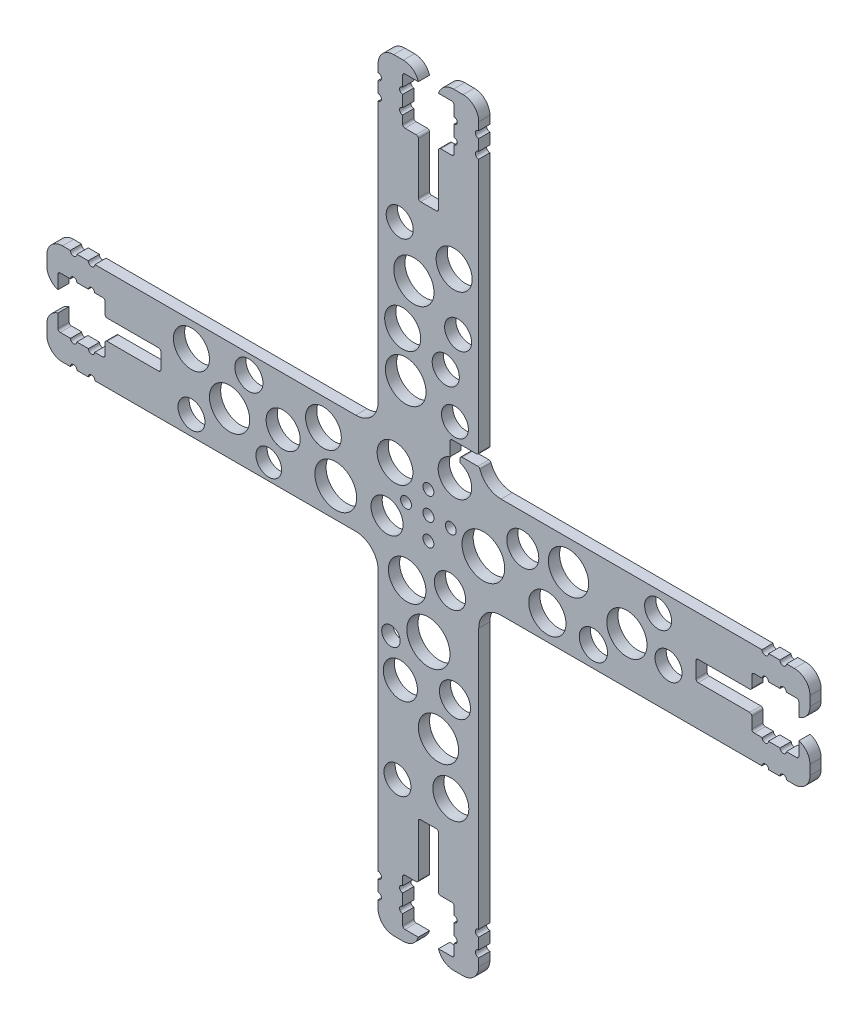
SolidWorks part; units mm, degrees
ref_plane "Front Plane" through (0, 0, 0) normal (0, 0, 1) x (1, 0, 0)
ref_plane "Top Plane" through (0, 0, 0) normal (0, 1, 0) x (1, 0, 0)
ref_plane "Right Plane" through (0, 0, 0) normal (1, 0, 0) x (0, 0, -1)
sketch "Esquisse1" plane through (0, 0, 0) normal (0, 0, 1) x (1, 0, 0)
  line L0 (0, 159.2308) -> (0, -15.7846) construction
  line L1 (-22.5, 22.5) -> (-22.5, 170.6346)
  line L2 (-22.5, 170.6346) -> (-4.5, 170.6346)
  line L3 (-4.5, 170.6346) -> (-4.5, 165.6346)
  line L4 (-4.5, 165.6346) -> (-11.5, 165.6346)
  line L5 (-11.5, 165.6346) -> (-11.5, 144.6346)
  line L6 (-11.5, 144.6346) -> (-4.5, 144.6346)
  line L7 (-4.5, 144.6346) -> (-4.5, 119.6346)
  line L8 (-4.5, 119.6346) -> (4.5, 119.6346)
  line L9 (4.5, 119.6346) -> (4.5, 144.6346)
  line L10 (4.5, 144.6346) -> (11.5, 144.6346)
  line L11 (11.5, 144.6346) -> (11.5, 165.6346)
  line L12 (11.5, 165.6346) -> (4.5, 165.6346)
  line L13 (4.5, 165.6346) -> (4.5, 170.6346)
  line L14 (4.5, 170.6346) -> (22.5, 170.6346)
  line L15 (22.5, 170.6346) -> (22.5, 22.5)
  line L16 (22.5, 22.5) -> (170.6346, 22.5)
  line L17 (170.6346, 22.5) -> (170.6346, 4.5)
  line L18 (170.6346, 4.5) -> (165.6346, 4.5)
  line L19 (165.6346, 4.5) -> (165.6346, 11.5)
  line L20 (165.6346, 11.5) -> (144.6346, 11.5)
  line L21 (144.6346, 11.5) -> (144.6346, 4.5)
  line L22 (144.6346, 4.5) -> (119.6346, 4.5)
  line L23 (119.6346, 4.5) -> (119.6346, -4.5)
  line L24 (119.6346, -4.5) -> (144.6346, -4.5)
  line L25 (144.6346, -4.5) -> (144.6346, -11.5)
  line L26 (144.6346, -11.5) -> (165.6346, -11.5)
  line L27 (165.6346, -11.5) -> (165.6346, -4.5)
  line L28 (165.6346, -4.5) -> (170.6346, -4.5)
  line L29 (170.6346, -4.5) -> (170.6346, -22.5)
  line L30 (170.6346, -22.5) -> (22.5, -22.5)
  line L31 (22.5, -22.5) -> (22.5, -170.6346)
  line L32 (22.5, -170.6346) -> (4.5, -170.6346)
  line L33 (4.5, -170.6346) -> (4.5, -165.6346)
  line L34 (4.5, -165.6346) -> (11.5, -165.6346)
  line L35 (11.5, -165.6346) -> (11.5, -144.6346)
  line L36 (11.5, -144.6346) -> (4.5, -144.6346)
  line L37 (4.5, -144.6346) -> (4.5, -119.6346)
  line L38 (4.5, -119.6346) -> (-4.5, -119.6346)
  line L39 (-4.5, -119.6346) -> (-4.5, -144.6346)
  line L40 (-4.5, -144.6346) -> (-11.5, -144.6346)
  line L41 (-11.5, -144.6346) -> (-11.5, -165.6346)
  line L42 (-11.5, -165.6346) -> (-4.5, -165.6346)
  line L43 (-4.5, -165.6346) -> (-4.5, -170.6346)
  line L44 (-4.5, -170.6346) -> (-22.5, -170.6346)
  line L45 (-22.5, -170.6346) -> (-22.5, -22.5)
  line L46 (-22.5, -22.5) -> (-170.6346, -22.5)
  line L47 (-170.6346, -22.5) -> (-170.6346, -4.5)
  line L48 (-170.6346, -4.5) -> (-165.6346, -4.5)
  line L49 (-165.6346, -4.5) -> (-165.6346, -11.5)
  line L50 (-165.6346, -11.5) -> (-144.6346, -11.5)
  line L51 (-144.6346, -11.5) -> (-144.6346, -4.5)
  line L52 (-144.6346, -4.5) -> (-119.6346, -4.5)
  line L53 (-119.6346, -4.5) -> (-119.6346, 4.5)
  line L54 (-119.6346, 4.5) -> (-144.6346, 4.5)
  line L55 (-144.6346, 4.5) -> (-144.6346, 11.5)
  line L56 (-144.6346, 11.5) -> (-165.6346, 11.5)
  line L57 (-165.6346, 11.5) -> (-165.6346, 4.5)
  line L58 (-165.6346, 4.5) -> (-170.6346, 4.5)
  line L59 (-170.6346, 4.5) -> (-170.6346, 22.5)
  line L60 (-170.6346, 22.5) -> (-22.5, 22.5)
  line L61 (-24.5698, 165.6346) -> (43.5937, 165.6346) construction
  line L62 (165.6346, 24.5698) -> (165.6346, -43.5937) construction
  line L63 (24.5698, -165.6346) -> (-43.5937, -165.6346) construction
  line L64 (-165.6346, -24.5698) -> (-165.6346, 43.5937) construction
  line L65 (-148.0023, 0) -> (163.5643, 0) construction
  circle A0 centre (0, 0) radius 2.5
  circle A1 centre (-80.2824, 14.1103) radius 6.2904
  circle A2 centre (-64.9494, 0.6296) radius 7.6187
  circle A3 centre (-41.4305, -9.3429) radius 9.3429
  circle A4 centre (-46.9444, 10.5137) radius 8
  circle A5 centre (-71.3951, -15.2254) radius 5.734
  circle A6 centre (42.1879, 8.0594) radius 7.1686
  circle A7 centre (24.5698, -3.6089) radius 9.551
  circle A8 centre (11.8627, 20.2507) radius 7.5
  circle A9 centre (-14.9441, 12.9829) radius 8
  circle A10 centre (-10.1433, 47.064) radius 9.0827
  circle A11 centre (11.8627, 42.1489) radius 6
  circle A12 centre (-18.5, -9.3429) radius 7.1678
  circle A13 centre (0, -49.0636) radius 9.6471
  circle A14 centre (-16.7647, -55.0598) radius 4.1145
  circle A15 centre (11.8627, -65.5127) radius 6.9485
  circle A16 centre (-12.5425, -70.0598) radius 7.6364
  circle A17 centre (9.6471, -24.3763) radius 6.9631
  circle A18 centre (-9.5049, -29.9285) radius 8.3862
  circle A19 centre (53.1834, -11.3064) radius 8.3279
  circle A20 centre (62.6447, 9.2453) radius 9
  circle A21 centre (13.2718, 76.5762) radius 6.033
  circle A22 centre (-11.5, 66.6049) radius 8.0615
  circle A23 centre (7.7598, 60.3029) radius 6.0616
  circle A24 centre (73.7695, -13.2445) radius 6.3276
  circle A25 centre (10, 0) radius 2.4404
  circle A26 centre (0, -10) radius 2.4404
  circle A27 centre (-10, 0) radius 2.4404
  circle A28 centre (0, 10) radius 2.4404
  circle A29 centre (4.5, -84.3396) radius 9
  circle A30 centre (88.7508, -1.4498) radius 9
  circle A31 centre (-88.9098, -3.1076) radius 9
  circle A32 centre (-6.4915, 87.5045) radius 9
  circle A34 centre (102.7074, 13.3403) radius 6.033
  circle A35 centre (107.3726, -4.5) radius 6.033
  circle A37 centre (-13.8334, -109.2151) radius 6.033
  circle A38 centre (-105.951, -13.9396) radius 6.033
  circle A39 centre (-12.8411, 107.1707) radius 6.033
  circle A40 centre (11.5, 101.0692) radius 8.0615
  circle A41 centre (10, -104.7403) radius 8.0615
  circle A42 centre (-105.951, 11.5) radius 8.0615
  point P19 (0, 119.6346)
  point P23 (0, 165.6346)
  point P74 (0, 0)
  point P76 (165.6346, 0)
  point P81 (0, -165.6346)
  point P84 (-165.6346, 0)
  point P129 (0, 162.6346)
  point P132 (162.6346, 0)
  point P133 (0, -162.6346)
  point P136 (-162.6346, 0)
  point P137 (90.1323, 0)
  point P144 (0, 0)
  point P147 (262.5433, 0)
  point P148 (4.5, -84.3396)
  point P151 (0, 0)
  point P154 (-6.4915, 87.5045)
  point P155 (0, 0)
  point P156 (0, 0)
  point P173 (11.5, 101.0692)
  point P174 (102.7074, -13.2445)
  point P175 (107.3726, -4.5)
  point P178 (9.6471, -104.7403)
  point P181 (-105.951, 11.5)
  dimension "D6" = 4
  dimension "D9" = 230
  dimension "D10" = 10
  dimension "D1" = 9
  dimension "D2" = 23
  dimension "D3" = 21
  dimension "D4" = 45
  dimension "D5" = 25
  dimension "D7" = 3
  dimension "D8" = 5
  dimension "D11" = 4
extrude "Boss.-Extru.1" add sketch "Esquisse1" along normal blind 5
fillet "Congé1" radius 7 16 edges at (170.6346, 4.5, 2.5) (170.6346, -4.5, 2.5) (4.5, -170.6346, 2.5) (-4.5, -170.6346, 2.5) (-170.6346, -4.5, 2.5) (-170.6346, 4.5, 2.5) (-4.5, 170.6346, 2.5) (4.5, 170.6346, 2.5) (22.5, 170.6346, 2.5) (-22.5, 170.6346, 2.5) (-170.6346, 22.5, 2.5) (-170.6346, -22.5, 2.5) (-22.5, -170.6346, 2.5) (22.5, -170.6346, 2.5) (170.6346, -22.5, 2.5) (170.6346, 22.5, 2.5)
fillet "Congé2" radius 10 4 edges at (-22.5, 22.5, 2.5) (22.5, 22.5, 2.5) (22.5, -22.5, 2.5) (-22.5, -22.5, 2.5)
fillet "Congé3" radius 1 32 edges at (165.6346, -11.5, 2.5) (144.6346, -11.5, 2.5) (119.6346, -4.5, 2.5) (165.6346, 11.5, 2.5) (144.6346, -4.5, 2.5) (144.6346, 11.5, 2.5) (119.6346, 4.5, 2.5) (144.6346, 4.5, 2.5) (11.5, 165.6346, 2.5) (11.5, 144.6346, 2.5) (4.5, 119.6346, 2.5) (4.5, 144.6346, 2.5) (-4.5, 119.6346, 2.5) (-4.5, 144.6346, 2.5) (-11.5, 144.6346, 2.5) (-11.5, 165.6346, 2.5) (-165.6346, 11.5, 2.5) (-144.6346, 11.5, 2.5) (-144.6346, 4.5, 2.5) (-119.6346, 4.5, 2.5) (-119.6346, -4.5, 2.5) (-144.6346, -4.5, 2.5) (-144.6346, -11.5, 2.5) (-165.6346, -11.5, 2.5) (-4.5, -119.6346, 2.5) (4.5, -119.6346, 2.5) (4.5, -144.6346, 2.5) (-4.5, -144.6346, 2.5) (11.5, -165.6346, 2.5) (11.5, -144.6346, 2.5) (-11.5, -165.6346, 2.5) (-11.5, -144.6346, 2.5)
sketch "Esquisse2" plane through (0, 0, 0) normal (0, 0, -1) x (-1, 0, 0)
  line L0 (-163.6346, 22.5) -> (-32.5, 22.5) construction
  line L2 (-83.3281, 0) -> (-132.2147, 0) construction
  line L3 (-160.1346, 22.5) -> (-157.1346, 22.5)
  line L4 (-152.1346, 22.5) -> (-149.1346, 22.5)
  line L5 (-160.1346, -22.5) -> (-157.1346, -22.5)
  line L6 (-152.1346, -22.5) -> (-149.1346, -22.5)
  line L7 (22.5, 160.1346) -> (22.5, 157.1346)
  line L8 (22.5, 152.1346) -> (22.5, 149.1346)
  line L9 (-22.5, 160.1346) -> (-22.5, 157.1346)
  line L10 (-22.5, 152.1346) -> (-22.5, 149.1346)
  line L11 (160.1346, -22.5) -> (157.1346, -22.5)
  line L12 (152.1346, -22.5) -> (149.1346, -22.5)
  line L13 (160.1346, 22.5) -> (157.1346, 22.5)
  line L14 (152.1346, 22.5) -> (149.1346, 22.5)
  line L15 (-22.5, -160.1346) -> (-22.5, -157.1346)
  line L16 (-22.5, -152.1346) -> (-22.5, -149.1346)
  line L17 (22.5, -160.1346) -> (22.5, -157.1346)
  line L18 (22.5, -152.1346) -> (22.5, -149.1346)
  line L19 (-145.6346, 11.5) -> (-164.6346, 11.5) construction
  line L20 (-158.6346, 24.0368) -> (-158.6346, 6.6966) construction
  line L21 (-150.6346, 24.0368) -> (-150.6346, 7.2406) construction
  line L22 (-157.2346, 11.5) -> (-160.0346, 11.5)
  line L23 (-152.0346, 11.5) -> (-149.2346, 11.5)
  line L24 (-152.0346, -11.5) -> (-149.2346, -11.5)
  line L25 (-157.2346, -11.5) -> (-160.0346, -11.5)
  line L26 (-11.5, 157.2346) -> (-11.5, 160.0346)
  line L27 (-11.5, 152.0346) -> (-11.5, 149.2346)
  line L28 (11.5, 157.2346) -> (11.5, 160.0346)
  line L29 (11.5, 152.0346) -> (11.5, 149.2346)
  line L30 (157.2346, 11.5) -> (160.0346, 11.5)
  line L31 (152.0346, 11.5) -> (149.2346, 11.5)
  line L32 (157.2346, -11.5) -> (160.0346, -11.5)
  line L33 (152.0346, -11.5) -> (149.2346, -11.5)
  line L34 (11.5, -157.2346) -> (11.5, -160.0346)
  line L35 (11.5, -152.0346) -> (11.5, -149.2346)
  line L36 (-11.5, -157.2346) -> (-11.5, -160.0346)
  line L37 (-11.5, -152.0346) -> (-11.5, -149.2346)
  line L38 (-165.6346, 10.5) -> (-165.6346, 4.5) construction
  arc A0 (-160.1346, 22.5) -> (-157.1346, 22.5) centre (-158.6346, 22.5) ccw
  arc A1 (-152.1346, 22.5) -> (-149.1346, 22.5) centre (-150.6346, 22.5) ccw
  arc A2 (-152.1346, -22.5) -> (-149.1346, -22.5) centre (-150.6346, -22.5) cw
  arc A3 (-160.1346, -22.5) -> (-157.1346, -22.5) centre (-158.6346, -22.5) cw
  arc A4 (22.5, 160.1346) -> (22.5, 157.1346) centre (22.5, 158.6346) ccw
  arc A5 (22.5, 152.1346) -> (22.5, 149.1346) centre (22.5, 150.6346) ccw
  arc A6 (-22.5, 160.1346) -> (-22.5, 157.1346) centre (-22.5, 158.6346) cw
  arc A7 (-22.5, 152.1346) -> (-22.5, 149.1346) centre (-22.5, 150.6346) cw
  arc A8 (160.1346, -22.5) -> (157.1346, -22.5) centre (158.6346, -22.5) ccw
  arc A9 (152.1346, -22.5) -> (149.1346, -22.5) centre (150.6346, -22.5) ccw
  arc A10 (160.1346, 22.5) -> (157.1346, 22.5) centre (158.6346, 22.5) cw
  arc A11 (152.1346, 22.5) -> (149.1346, 22.5) centre (150.6346, 22.5) cw
  arc A12 (-22.5, -160.1346) -> (-22.5, -157.1346) centre (-22.5, -158.6346) ccw
  arc A13 (-22.5, -152.1346) -> (-22.5, -149.1346) centre (-22.5, -150.6346) ccw
  arc A14 (22.5, -160.1346) -> (22.5, -157.1346) centre (22.5, -158.6346) cw
  arc A15 (22.5, -152.1346) -> (22.5, -149.1346) centre (22.5, -150.6346) cw
  arc A16 (-157.2346, 11.5) -> (-160.0346, 11.5) centre (-158.6346, 11.5) ccw
  arc A17 (-152.0346, 11.5) -> (-149.2346, 11.5) centre (-150.6346, 11.5) cw
  arc A18 (-152.0346, -11.5) -> (-149.2346, -11.5) centre (-150.6346, -11.5) ccw
  arc A19 (-157.2346, -11.5) -> (-160.0346, -11.5) centre (-158.6346, -11.5) cw
  arc A20 (-11.5, 157.2346) -> (-11.5, 160.0346) centre (-11.5, 158.6346) cw
  arc A21 (-11.5, 152.0346) -> (-11.5, 149.2346) centre (-11.5, 150.6346) ccw
  arc A22 (11.5, 157.2346) -> (11.5, 160.0346) centre (11.5, 158.6346) ccw
  arc A23 (11.5, 152.0346) -> (11.5, 149.2346) centre (11.5, 150.6346) cw
  arc A24 (157.2346, 11.5) -> (160.0346, 11.5) centre (158.6346, 11.5) cw
  arc A25 (152.0346, 11.5) -> (149.2346, 11.5) centre (150.6346, 11.5) ccw
  arc A26 (157.2346, -11.5) -> (160.0346, -11.5) centre (158.6346, -11.5) ccw
  arc A27 (152.0346, -11.5) -> (149.2346, -11.5) centre (150.6346, -11.5) cw
  arc A28 (11.5, -157.2346) -> (11.5, -160.0346) centre (11.5, -158.6346) cw
  arc A29 (11.5, -152.0346) -> (11.5, -149.2346) centre (11.5, -150.6346) ccw
  arc A30 (-11.5, -157.2346) -> (-11.5, -160.0346) centre (-11.5, -158.6346) ccw
  arc A31 (-11.5, -152.0346) -> (-11.5, -149.2346) centre (-11.5, -150.6346) cw
  point P58 (0, 0)
  dimension "D1" = 5.5
  dimension "D2" = 5
  dimension "D3" = 3
  dimension "D4" = 3
  dimension "D5" = 4
extrude "Enlèv. mat.-Extru.1" cut sketch "Esquisse2" against normal blind 5
sketch "Esquisse3" plane through (0, 0, 0) normal (0, 0, -1) x (-1, 0, 0)
  line L0 (-23.0619, 34.5102) -> (-9.6127, 34.5102)
  line L2 (-9.6127, 34.5102) -> (-9.6127, 27.4052)
  line L3 (-9.6127, 27.4052) -> (-14.1127, 27.4052)
  line L4 (-14.1127, 27.4052) -> (-14.1127, 30.0102)
  line L5 (-14.1127, 30.0102) -> (-23.0619, 30.0102)
  line L6 (-23.0619, 30.0102) -> (-23.0619, 34.5102)
  circle A0 centre (-11.8627, 20.2507) radius 7.5 construction
  dimension "D1" = 4.5
  dimension "D2" = 4.5
extrude "Enlèv. mat.-Extru.2" cut sketch "Esquisse3" against normal blind 10
fillet "Congé4" radius 1 4 edges at (22.5, 34.5102, 2.5) (22.8149, 30.0102, 2.5) (9.6127, 34.5102, 2.5) (14.1127, 30.0102, 2.5)
